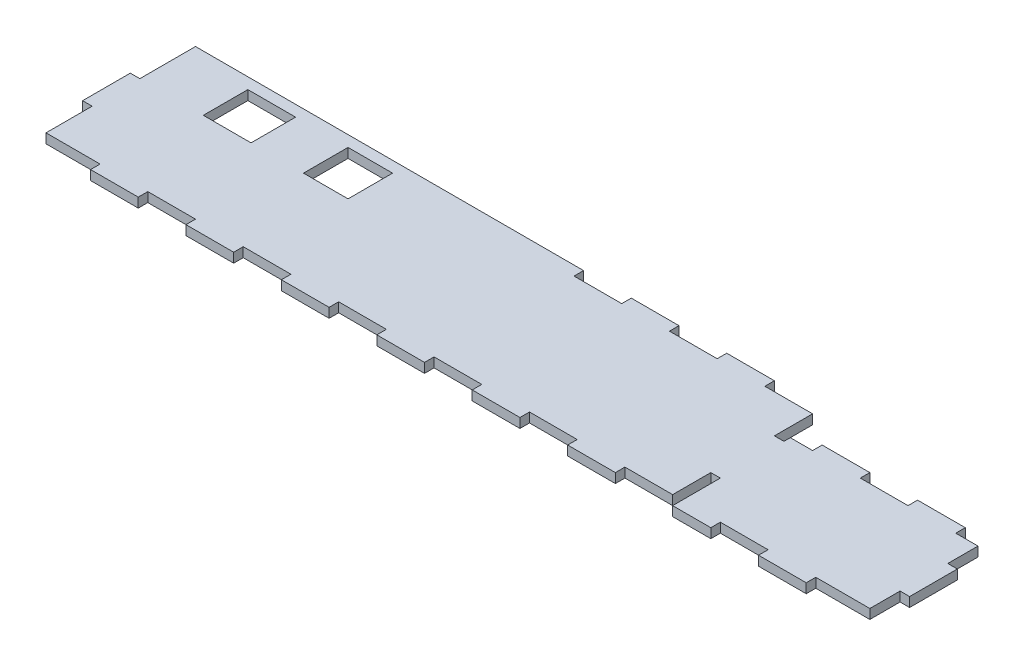
SolidWorks part; units mm, degrees
ref_plane "Alzado" through (0, 0, 0) normal (0, 0, 1) x (1, 0, 0)
ref_plane "Planta" through (0, 0, 0) normal (0, 1, 0) x (1, 0, 0)
ref_plane "Vista lateral" through (0, 0, 0) normal (1, 0, 0) x (0, 0, -1)
sketch "Croquis1" plane through (0, 0, 0) normal (0, 1, 0) x (1, 0, 0)
  line L0 (125, 50) -> (3, 50)
  line L1 (20, 50) -> (35, 50)
  line L2 (197, 3) -> (200, 3)
  line L3 (20, 0) -> (35, 0)
  line L4 (265, 12.5) -> (265, 27.5)
  line L5 (255, 40) -> (240, 40)
  line L6 (0, 25) -> (0, 32.5)
  line L7 (0, 32.5) -> (3, 32.5)
  line L8 (3, 32.5) -> (3, 47)
  line L9 (200, 15) -> (203, 15)
  line L10 (110, 47) -> (95, 47) construction
  line L11 (95, 47) -> (95, 50) construction
  line L12 (95, 50) -> (80, 50)
  line L13 (80, 50) -> (80, 47) construction
  line L14 (80, 47) -> (65, 47) construction
  line L15 (65, 47) -> (65, 50) construction
  line L16 (65, 50) -> (50, 50)
  line L17 (50, 50) -> (50, 47) construction
  line L18 (50, 47) -> (35, 47) construction
  line L19 (35, 47) -> (35, 50) construction
  line L20 (35, 50) -> (20, 50)
  line L21 (20, 50) -> (20, 47) construction
  line L22 (20, 47) -> (3, 47) construction
  line L23 (185, 47) -> (196.5, 47)
  line L24 (185, 50) -> (185, 47)
  line L25 (170, 47) -> (170, 50)
  line L26 (155, 47) -> (170, 47)
  line L27 (155, 50) -> (155, 47)
  line L28 (140, 47) -> (140, 50)
  line L29 (125, 47) -> (140, 47)
  line L30 (125, 50) -> (125, 47)
  line L31 (110, 47) -> (110, 50) construction
  line L32 (0, 25) -> (0, 17.5)
  line L33 (203, 15) -> (203, 0)
  line L34 (0, 17.5) -> (3, 17.5)
  line L35 (3, 17.5) -> (3, 3)
  line L36 (225, 40) -> (210, 40)
  line L37 (140, 3) -> (125, 3)
  line L38 (125, 3) -> (125, 0)
  line L39 (125, 0) -> (110, 0)
  line L40 (110, 0) -> (110, 3)
  line L41 (110, 3) -> (95, 3)
  line L42 (95, 3) -> (95, 0)
  line L43 (95, 0) -> (80, 0)
  line L44 (80, 0) -> (80, 3)
  line L45 (80, 3) -> (65, 3)
  line L46 (65, 3) -> (65, 0)
  line L47 (65, 0) -> (50, 0)
  line L48 (50, 0) -> (50, 3)
  line L49 (50, 3) -> (35, 3)
  line L50 (35, 3) -> (35, 0)
  line L51 (35, 0) -> (20, 0)
  line L52 (20, 0) -> (20, 3)
  line L53 (20, 3) -> (3, 3)
  line L54 (245, 3) -> (262, 3)
  line L55 (245, 0) -> (245, 3)
  line L56 (230, 3) -> (230, 0)
  line L57 (215, 3) -> (230, 3)
  line L58 (215, 0) -> (215, 3)
  line L59 (3, 50) -> (3, 47)
  line L60 (185, 3) -> (197, 3)
  line L61 (185, 0) -> (185, 3)
  line L62 (170, 3) -> (170, 0)
  line L63 (155, 3) -> (170, 3)
  line L64 (155, 0) -> (155, 3)
  line L65 (140, 3) -> (140, 0)
  line L66 (255, 40) -> (240, 40)
  line L67 (200, 35) -> (203, 35)
  line L68 (225, 37) -> (240, 37)
  line L69 (240, 37) -> (240, 40)
  line L70 (240, 40) -> (255, 40)
  line L71 (255, 40) -> (255, 37)
  line L72 (255, 37) -> (262, 37)
  line L73 (210, 37) -> (203, 37)
  line L74 (210, 40) -> (210, 37)
  line L75 (225, 37) -> (225, 40)
  line L76 (203, 35) -> (203, 37)
  line L78 (265, 20) -> (265, 27.5)
  line L79 (265, 27.5) -> (262, 27.5)
  line L80 (262, 27.5) -> (262, 37)
  line L81 (265, 20) -> (265, 12.5)
  line L82 (265, 12.5) -> (262, 12.5)
  line L83 (262, 12.5) -> (262, 3)
  line L85 (196.5, 47) -> (200, 47)
  line L87 (200, 35) -> (200, 37)
  line L89 (200, 15) -> (200, 3)
  line L90 (0, 17.5) -> (0, 32.5)
  line L91 (50, 0) -> (65, 0)
  line L92 (80, 0) -> (95, 0)
  line L93 (110, 0) -> (125, 0)
  line L94 (140, 0) -> (155, 0)
  line L95 (170, 0) -> (185, 0)
  line L96 (203, 0) -> (215, 0)
  line L97 (230, 0) -> (245, 0)
  line L98 (170, 50) -> (185, 50)
  line L99 (140, 50) -> (155, 50)
  line L100 (50, 50) -> (65, 50)
  line L101 (80, 50) -> (95, 50)
  line L102 (110, 50) -> (125, 50)
  line L103 (200, 47) -> (200, 37)
  dimension "D3" = 17
  dimension "D4" = 3
  dimension "D5" = 7.5
  dimension "D6" = 3
  dimension "D7" = 11.5
  dimension "D8" = 15
  dimension "D9" = 15
  dimension "D10" = 15
  dimension "D11" = 15
  dimension "D12" = 15
  dimension "D13" = 15
  dimension "D14" = 7.5
  dimension "D15" = 15
  dimension "D16" = 3
  dimension "D17" = 15
  dimension "D18" = 15
  dimension "D19" = 15
  dimension "D20" = 15
  dimension "D21" = 15
  dimension "D22" = 15
  dimension "D23" = 15
  dimension "D24" = 2
  dimension "D25" = 7
  dimension "D26" = 15
  dimension "D27" = 7.5
  dimension "D28" = 3
  dimension "D29" = 7.5
  dimension "D30" = 3
  dimension "D31" = 3
  dimension "D32" = 3
  dimension "D33" = 15
  dimension "D34" = 15
  dimension "D35" = 15
  dimension "D36" = 15
  dimension "D37" = 12
  dimension "D38" = 3
  dimension "D39" = 12
  dimension "D40" = 15
  dimension "D41" = 15
  dimension "D42" = 17
  dimension "D43" = 3
  dimension "D44" = 3
  dimension "D45" = 3
  dimension "D46" = 17
  dimension "D47" = 3
  dimension "D48" = 3
  dimension "D49" = 12
  dimension "D50" = 3
  dimension "D51" = 3
  dimension "D52" = 3
  dimension "D53" = 3
extrude "Saliente-Extruir1" add sketch "Croquis1" along normal blind 3 contours L102 L31 L10 L11 L12 L13 L14 L15 L16 L17 L18 L19 L1 L21 L22 L8 L7 L6 L32 L34 L35 L53 L52 L3 L50 L49 L48 L47 L46 L45 L44 L43 L42 L41 L40 L39 L38 L37 L65 L94 L64 L63 L62 L95 L61 L60 L89 L96 region at (125.8487, 0, -24.4393)
sketch "Sketch1" plane through (0, 3, 0) normal (0, 1, 0) x (1, 0, 0)
  line L0 (125, 50) -> (3, 50) construction
  line L1 (22.96, 46.5) -> (37.96, 46.5)
  line L2 (22.96, 46.5) -> (22.96, 32.5)
  line L3 (22.96, 32.5) -> (37.96, 32.5)
  line L4 (37.96, 46.5) -> (37.96, 32.5)
  line L5 (22.96, 46.5) -> (37.96, 32.5) construction
  line L6 (22.96, 32.5) -> (37.96, 46.5) construction
  line L7 (0, 17.5) -> (0, 32.5) construction
  line L8 (30.46, 39.5) -> (61.45, 39.5) construction
  line L10 (54.45, 46.5) -> (68.45, 46.5)
  line L11 (54.45, 46.5) -> (54.45, 32.5)
  line L12 (54.45, 32.5) -> (68.45, 32.5)
  line L13 (68.45, 46.5) -> (68.45, 32.5)
  line L14 (54.45, 46.5) -> (68.45, 32.5) construction
  line L15 (54.45, 32.5) -> (68.45, 46.5) construction
  point P0 (30.46, 39.5)
  dimension "D1" = 15
  dimension "D2" = 14
  dimension "D3" = 10.5
  dimension "D4" = 30.46
  dimension "D5" = 14
  dimension "D6" = 14
  dimension "D7" = 54.45
extrude "Cut-Extrude1" cut sketch "Sketch1" against normal blind 10
